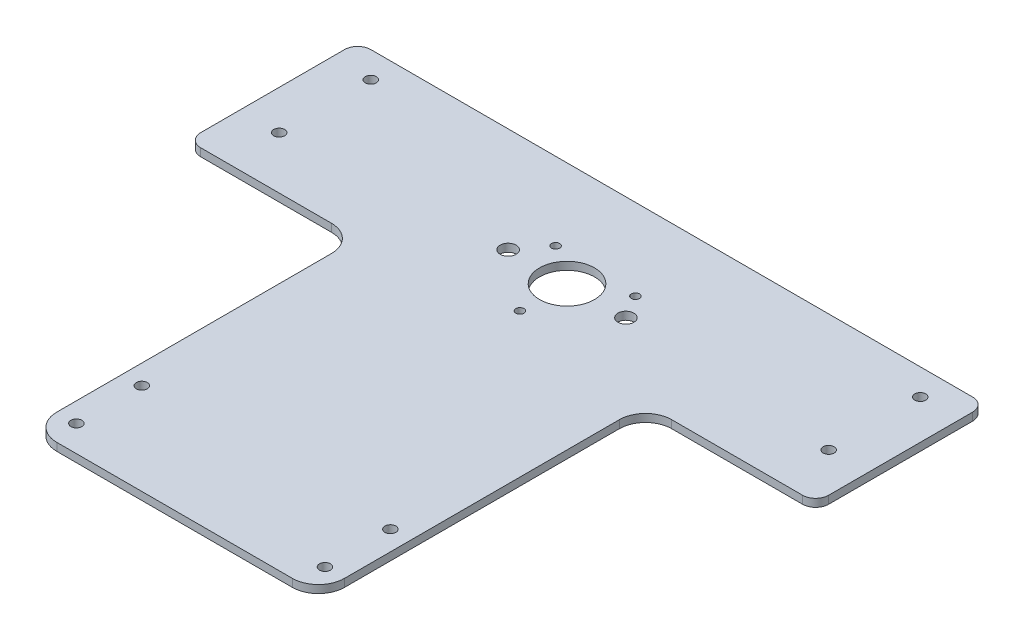
SolidWorks part; units mm, degrees
material "Thornel Mat VMA"
ref_plane "前视基准面" through (0, 0, 0) normal (0, 0, 1) x (1, 0, 0)
ref_plane "上视基准面" through (0, 0, 0) normal (0, 1, 0) x (1, 0, 0)
ref_plane "右视基准面" through (0, 0, 0) normal (1, 0, 0) x (0, 0, -1)
sketch "草图1" plane through (0, 0, 0) normal (0, 1, 0) x (1, 0, 0)
  line L0 (-105, 55.625) -> (-105, -9.375) construction
  line L1 (-120, -9.375) -> (120, -9.375)
  line L2 (-120, -9.375) -> (-120, 55.625)
  line L3 (-120, 55.625) -> (120, 55.625)
  line L4 (120, -9.375) -> (120, 55.625)
  line L5 (-120, -9.375) -> (120, 55.625) construction
  line L6 (-120, 55.625) -> (120, -9.375) construction
  line L7 (0, 55.625) -> (0, -9.375) construction
  line L8 (0, -71.875) -> (0, -9.375) construction
  line L9 (-66.9961, -9.375) -> (13.0039, -9.375)
  line L11 (-55, -134.375) -> (55, -134.375)
  line L12 (-55, -134.375) -> (-55, -9.375)
  line L13 (-55, -9.375) -> (55, -9.375)
  line L14 (55, -134.375) -> (55, -9.375)
  line L15 (-55, -134.375) -> (55, -9.375) construction
  line L16 (-55, -9.375) -> (55, -134.375) construction
  circle A0 centre (-105, 45.625) radius 2.1
  circle A1 centre (-105, 10.625) radius 2.1
  circle A2 centre (105, 10.625) radius 2.1
  circle A3 centre (105, 45.625) radius 2.1
  point P0 (0, 23.125)
  dimension "D1" = 65
  dimension "D2" = 240
  dimension "D3" = 15
  dimension "D4" = 35
  dimension "D5" = 20
  dimension "D6" = 125
  dimension "D7" = 55
extrude "凸台-拉伸1" add sketch "草图1" along normal blind 3 contours L1 L4 L3 L2 A2 A1 A0 A3 | L11 L14 L1 L9 L12 region at (0, 0, -23.1072) region at (0, 0, 71.875)
sketch "草图5" plane through (0, 3, 0) normal (0, 1, 0) x (1, 0, 0)
  line L0 (0, 0) -> (0, -71.875) construction
  line L2 (-55, -134.375) -> (55, -134.375)
  line L3 (-55, -134.375) -> (-55, -9.375)
  line L5 (55, -134.375) -> (55, -9.375)
  line L6 (-55, -134.375) -> (55, -9.375) construction
  line L7 (-55, -9.375) -> (55, -134.375) construction
  line L8 (-47.5, -124.375) -> (47.5, -124.375) construction
  line L9 (47.5, -124.375) -> (47.5, -99.375) construction
  line L10 (-55, -9.375) -> (55, -9.375)
  line L11 (-120, -9.375) -> (-55, -9.375) construction
  circle A0 centre (-47.5, -124.375) radius 2.1
  circle A2 centre (47.5, -124.375) radius 2.1
  circle A3 centre (47.5, -99.375) radius 2.1
  circle A4 centre (-47.5, -99.375) radius 2.1
  point P12 (0, -124.375)
  point P18 (0, 0)
  dimension "D6" = 4.2
  dimension "D7" = 4.2
  dimension "D1" = 125
  dimension "D2" = 110
  dimension "D3" = 95
  dimension "D4" = 25
  dimension "D5" = 10
  dimension "D8" = 0
sketch "草图3" plane through (0, 3, 0) normal (0, 1, 0) x (1, 0, 0)
  line L2 (0, 59.375) -> (0, -28.125) construction
  line L3 (-120, 55.625) -> (120, 55.625) construction
  line L4 (-22.5, 15.625) -> (22.5, 15.625) construction
  circle A0 centre (0, 15.625) radius 10.5
  circle A1 centre (0, -2.375) radius 1.55
  circle A2 centre (-14.7211, 25.9831) radius 1.55
  circle A3 centre (17.1983, 24.5529) radius 1.55
  circle A4 centre (-22.5, 15.625) radius 3.05
  circle A5 centre (22.5, 15.625) radius 3.05
  point P16 (0.8257, 16.0537)
  point P18 (0, 15.625)
  dimension "D1" = 3
  dimension "D4" = 6.1
  dimension "D5" = 6.1
  dimension "D2" = 40
  dimension "D3" = 45
  dimension "D6" = 18
  dimension "D7" = 18
fillet "圆角1" radius 5 4 edges at (120, 1.5, 9.375) (-120, 1.5, 9.375) (-120, 1.5, -55.625) (120, 1.5, -55.625)
extrude "切除-拉伸4" cut sketch "草图5" against normal blind 10 contours A3 | A2 | A4 | A0
fillet "圆角2" radius 10 4 edges at (55, 1.5, 9.375) (55, 1.5, 134.375) (-55, 1.5, 134.375) (-55, 1.5, 9.375)
extrude "切除-拉伸5" cut sketch "草图3" against normal blind 10
